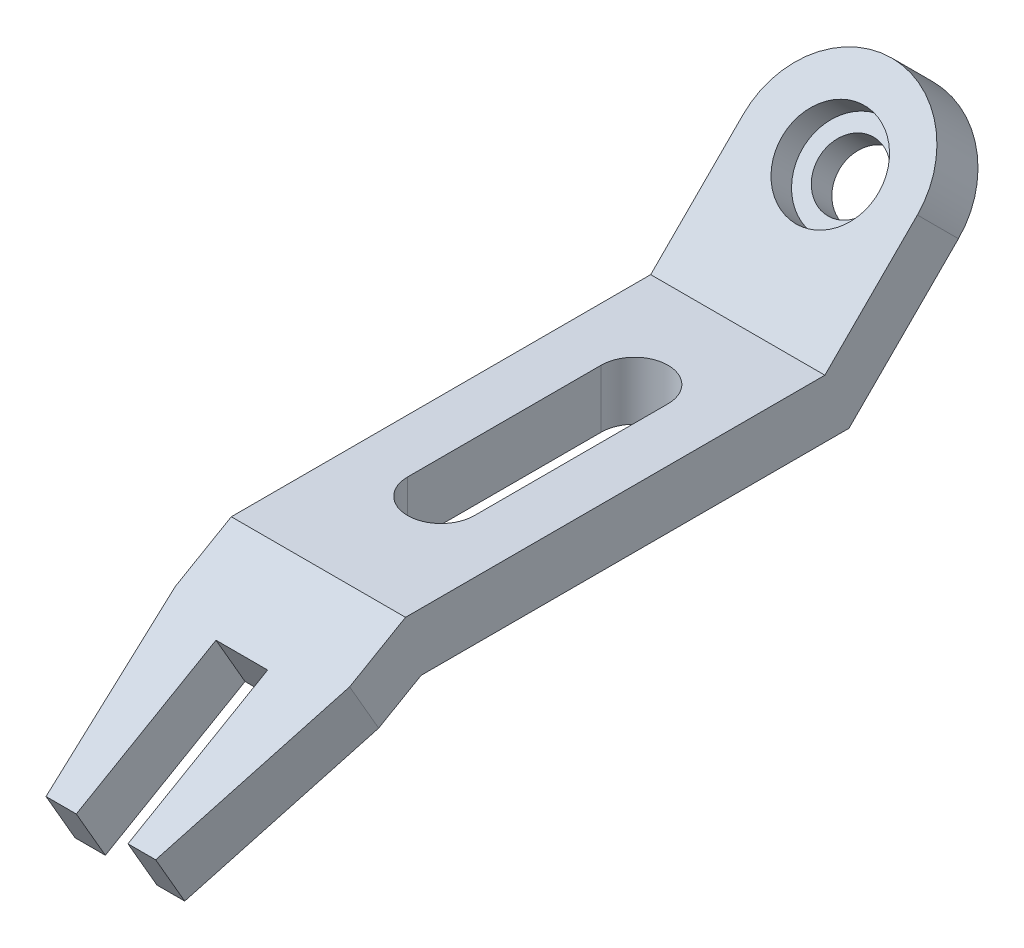
SolidWorks part; units mm, degrees
ref_plane "Front Plane" through (0, 0, 0) normal (0, 0, 1) x (1, 0, 0)
ref_plane "Top Plane" through (0, 0, 0) normal (0, 1, 0) x (1, 0, 0)
ref_plane "Right Plane" through (0, 0, 0) normal (1, 0, 0) x (0, 0, -1)
sketch "Sketch1" plane through (0, 0, 0) normal (1, 0, 0) x (0, 0, -1)
  line L0 (-59.1115, 0) -> (73.5212, 0)
  line L1 (73.5212, 0) -> (107.4624, 33.9411)
  line L2 (107.4624, 33.9411) -> (94.7344, 46.669)
  line L3 (94.7344, 46.669) -> (66.0654, 18)
  line L4 (66.0654, 18) -> (-63.9346, 18)
  line L5 (-63.9346, 18) -> (-81.2551, 8)
  line L6 (-81.2551, 8) -> (-72.2551, -7.5885)
  line L7 (-72.2551, -7.5885) -> (-59.1115, 0)
  point P7 (0, 0)
  point P10 (0, 0)
  dimension "D1" = 130
  dimension "D2" = 135
  dimension "D3" = 48
  dimension "D4" = 18
  dimension "D5" = 18
  dimension "D6" = 150
  dimension "D7" = 18
  dimension "D8" = 20
extrude "Boss-Extrude1" add sketch "Sketch1" against normal blind 54
sketch "Sketch2" plane through (0, 41.1845, 23.7779) normal (0, 0.866, 0.5) x (1, 0, 0)
  line L0 (0, -66.369) -> (-11.6267, -122.369)
  line L1 (0, -66.369) -> (-54, -66.369)
  line L2 (-54, -66.369) -> (-45.6267, -122.369)
  line L3 (-45.6267, -122.369) -> (-36.2306, -122.369)
  line L4 (-36.2306, -122.369) -> (-36.2306, -72.369)
  line L5 (-36.2306, -72.369) -> (-20.2306, -72.369)
  line L6 (-20.2306, -72.369) -> (-20.2306, -122.369)
  line L7 (-20.2306, -122.369) -> (-11.6267, -122.369)
  line L8 (-54, -46.369) -> (0, -46.369) construction
  line L9 (-54, -66.369) -> (-54, -72.369)
  line L10 (-54, -46.369) -> (-54, -66.369) construction
  line L12 (0, -46.369) -> (0, -66.369) construction
  line L13 (0, -72.369) -> (0, -66.369)
  line M12 (-54, -66.369) -> (0, -66.369)
  dimension "D1" = 34
  dimension "D2" = 16
  dimension "D3" = 50
  dimension "D4" = 76
extrude "Boss-Extrude2" add sketch "Sketch2" against normal blind 18 contours L6 L7 L0 L2 L3 L4 L5 M12 region at (-6.575, -5.9209, 105.3669)
sketch "Sketch4" plane through (0, -24.0327, -24.0327) normal (0, 0.7071, 0.7071) x (1, 0, 0)
  line L0 (-54, 99.9874) -> (0, 99.9874) construction
  circle A0 centre (-27, 99.9874) radius 27
  circle A1 centre (-27, 99.9874) radius 15
  circle A2 centre (-27, 99.9874) radius 10
  line M3 (0, 99.9874) -> (-54, 99.9874)
  dimension "D1" = 30
  dimension "D2" = 20
extrude "Boss-Extrude4" add sketch "Sketch4" against normal blind 18 contours A1 A0 M3 | A1 A0 M3 region at (-6, 47.096, -95.1614) region at (-27, 28.0041, -76.0695)
extrude "Cut-Extrude1" cut sketch "Sketch4<4>" against normal blind 18 contours A2 M3 region at (-27, 43.668, -91.7334)
sketch "Sketch4<4>" plane through (0, -24.0327, -24.0327) normal (0, 0.7071, 0.7071) x (1, 0, 0) same geometry as "Sketch4"
extrude "Boss-Extrude5" add sketch "Sketch4<5>" against normal blind 18 contours A2 A1 M3 region at (-14.5, 46.9062, -94.9716)
sketch "Sketch4<5>" plane through (0, -24.0327, -24.0327) normal (0, 0.7071, 0.7071) x (1, 0, 0) same geometry as "Sketch4"
extrude "Cut-Extrude2" cut sketch "Sketch4<6>" against normal blind 9 contours A2 A1 M3 | A2 A1 M3 region at (-14.5, 46.9062, -94.9716) region at (-27, 36.2996, -84.365)
sketch "Sketch4<6>" plane through (0, -24.0327, -24.0327) normal (0, 0.7071, 0.7071) x (1, 0, 0) same geometry as "Sketch4"
sketch "Sketch5" plane through (0, 18, 0) normal (0, 1, 0) x (1, 0, 0)
  line L0 (-27, -25.9346) -> (-27, 34.0654)
  line L1 (-27, -25.9346) -> (-27, 34.0654) construction
  line L2 (-37.3657, -25.9346) -> (-37.3657, 34.0654)
  line L3 (-16.6343, -25.9346) -> (-16.6343, 34.0654)
  line L4 (-54, -63.9346) -> (0, -63.9346) construction
  arc A0 (-37.3657, -25.9346) -> (-16.6343, -25.9346) centre (-27, -25.9346) ccw
  arc A1 (-16.6343, 34.0654) -> (-37.3657, 34.0654) centre (-27, 34.0654) ccw
  point P2 (-27, 4.0654)
  dimension "D1" = 60
  dimension "D2" = 38
extrude "Cut-Extrude3" cut sketch "Sketch5" against normal through all contours L3 A1 L2 A0 region at (-36.5322, 18, -4.0654)
